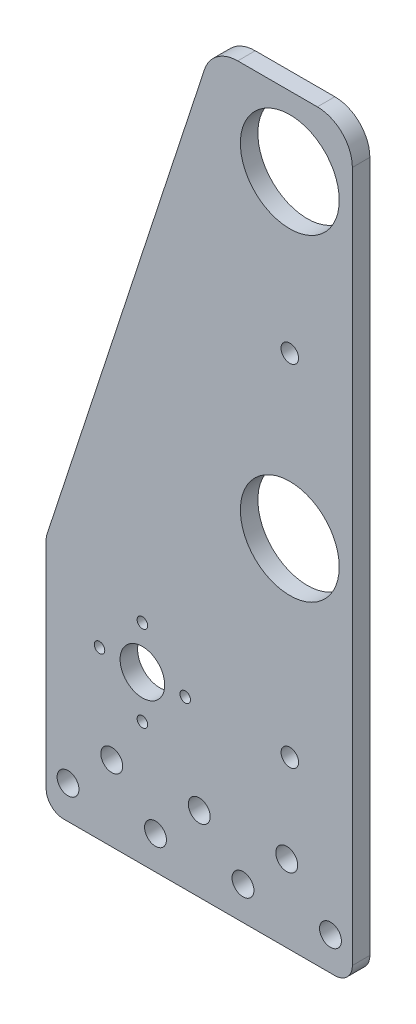
SolidWorks part; units mm, degrees
ref_plane "Front Plane" through (0, 0, 0) normal (0, 0, 1) x (1, 0, 0)
ref_plane "Top Plane" through (0, 0, 0) normal (0, 1, 0) x (1, 0, 0)
ref_plane "Right Plane" through (0, 0, 0) normal (1, 0, 0) x (0, 0, -1)
sketch "Sketch1" plane through (0, 0, 0) normal (0, 0, 1) x (1, 0, 0)
  line L2 (88.9, 205.74) -> (88.9, 5.08)
  line L3 (83.82, 0) -> (5.08, 0)
  line L4 (78.74, 215.9) -> (55.6253, 215.9)
  line L5 (45.9692, 208.9) -> (0.252, 69.2)
  line L6 (0, 67.62) -> (0, 5.08)
  line L7 (6.35, 9.652) -> (31.75, 9.652) construction
  circle A0 centre (70.739, 195.58) radius 14.351
  circle A1 centre (70.739, 103.378) radius 14.351
  circle A2 centre (70.739, 149.954) radius 2.54
  circle A3 centre (70.739, 48.354) radius 2.54
  arc A4 (78.74, 215.9) -> (88.9, 205.74) centre (78.74, 205.74) cw
  arc A5 (0, 5.08) -> (5.08, 0) centre (5.08, 5.08) ccw
  arc A6 (88.9, 5.08) -> (83.82, 0) centre (83.82, 5.08) cw
  arc A7 (55.6253, 215.9) -> (45.9692, 208.9) centre (55.6253, 205.74) ccw
  arc A8 (0.252, 69.2) -> (0, 67.62) centre (5.08, 67.62) ccw
  circle A9 centre (27.94, 48.354) radius 6.477
  circle A10 centre (27.94, 35.908) radius 1.524
  circle A14 centre (15.494, 48.354) radius 1.524
  circle A15 centre (27.94, 60.8) radius 1.524
  circle A16 centre (40.386, 48.354) radius 1.524
  circle A17 centre (70.739, 195.58) radius 50.8 construction
  circle A18 centre (70.739, 103.378) radius 38.1 construction
  circle A19 centre (6.35, 9.652) radius 3.175
  circle A21 centre (31.75, 9.652) radius 3.175
  circle A22 centre (57.15, 9.652) radius 3.175
  circle A23 centre (82.55, 9.652) radius 3.175
  circle A29 centre (69.85, 22.352) radius 3.175
  circle A30 centre (44.45, 21.844) radius 3.175
  circle A31 centre (19.05, 21.844) radius 3.175
  point P17 (88.9, 215.9)
  point P20 (0, 0)
  point P23 (88.9, 0)
  point P25 (48.26, 215.9)
  point P26 (48.26, 215.9)
  point P42 (34.6916, 35.4)
  point P43 (27.94, 48.354)
  dimension "D1" = 28.702
  dimension "D2" = 28.702
  dimension "D4" = 88.9
  dimension "D7" = 5.08
  dimension "D9" = 5.08
  dimension "D11" = 10.16
  dimension "D12" = 5.08
  dimension "D13" = 10.16
  dimension "D14" = 5.08
  dimension "D16" = 12.954
  dimension "D17" = 3.048
  dimension "D23" = 139.7
  dimension "D24" = 101.6
  dimension "D25" = 76.2
  dimension "D26" = 6.35
  dimension "D29" = 21.844
  dimension "D31" = 6.35
  dimension "D32" = 4
  dimension "D34" = 19.05
  dimension "D39" = 21.844
  dimension "D30" = 6.35
  dimension "D35" = 6.35
  dimension "D37" = 6.35
  dimension "D38" = 25.4
  dimension "D3" = 92.202
  dimension ".715" = 18.161
  dimension "D5" = 215.9
  dimension "D6" = 20.32
  dimension "D8" = 45.626
  dimension "D10" = 101.6
  dimension "D15" = 40.64
  dimension "D18" = 12.446
  dimension "D20" = 27.94
  dimension "D21" = 12.446
  dimension "D22" = 12.446
  dimension "D27" = 9.652
  dimension "D28" = 25.4
  dimension "D33" = 12.7
  dimension "D36" = 25.4
  dimension "D19" = 4
extrude "Boss-Extrude1" add sketch "Sketch1" along normal blind 5.08
